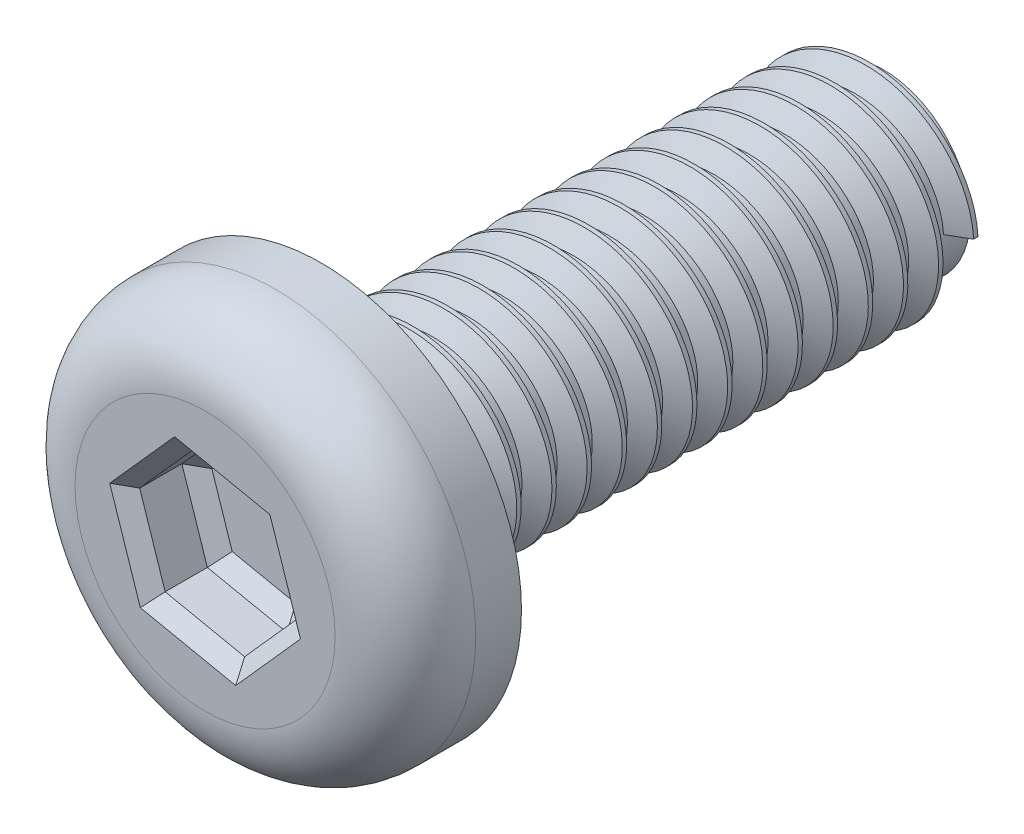
SolidWorks part; units mm, degrees
ref_plane "前视基准面" through (0, 0, 0) normal (0, 0, 1) x (1, 0, 0)
ref_plane "上视基准面" through (0, 0, 0) normal (0, 1, 0) x (1, 0, 0)
ref_plane "右视基准面" through (0, 0, 0) normal (1, 0, 0) x (0, 0, -1)
sketch "草图1" plane through (0, 0, 0) normal (0, 0, 1) x (1, 0, 0)
  circle A0 centre (0, 0) radius 2.85
  dimension "D1" = 5.7
extrude "凸台-拉伸1" add sketch "草图1" along normal blind 1.65
sketch "草图2" plane through (0, 0, 0) normal (0, 0, -1) x (-1, 0, 0)
  circle A0 centre (0, 0) radius 1.2295
  dimension "D1" = 2.459
extrude "凸台-拉伸2" add sketch "草图2" along normal blind 8
fillet "圆角1" radius 1 1 edges at (2.85, 0, 1.65)
sketch "草图3" plane through (0, 0, 1.65) normal (0, 0, 1) x (1, 0, 0)
  line L1 (0.3622, -1.0964) -> (1.1306, -0.2345)
  line L2 (1.1306, -0.2345) -> (0.7684, 0.8619)
  line L3 (0.7684, 0.8619) -> (-0.3622, 1.0964)
  line L4 (-0.3622, 1.0964) -> (-1.1306, 0.2345)
  line L5 (-1.1306, 0.2345) -> (-0.7684, -0.8619)
  line L6 (-0.7684, -0.8619) -> (0.3622, -1.0964)
  circle A0 centre (0, 0) radius 1 construction
  dimension "D1" = 2
extrude "切除-拉伸1" cut sketch "草图3" against normal blind 1
chamfer "倒角1" distance 0.2 angle 45 12 edges at (0.7464, -0.6655, 1.65) (0.9495, 0.3137, 1.65) (0.2031, 0.9792, 1.65) (-0.7464, 0.6655, 1.65) (-0.9495, -0.3137, 1.65) (-0.2031, -0.9792, 1.65) (-0.9495, -0.3137, 0.65) (-0.7464, 0.6655, 0.65) (0.2031, 0.9792, 0.65) (0.9495, 0.3137, 0.65) (0.7464, -0.6655, 0.65) (-0.2031, -0.9792, 0.65)
thread "螺纹线1" pitch 0.5 method extrude profile "螺纹线轮廓2" start angle 0, offset 0, length 0, pitch 0.5, diameter 2.459
ref_plane "基准面2" through (1.2295, 0, -8) normal (0, -1, 0) x (1, 0, 0)
sketch "螺纹线轮廓2" plane through (1.2295, 0, -8) normal (0, -1, 0) x (1, 0, 0)
  line L0 (0, 0) -> (0, 0.5) construction
  line L1 (0, 0) -> (0.2706, 0.1562)
  line L2 (0.2706, 0.1562) -> (0.2706, 0.2187)
  line L3 (0.2706, 0.2187) -> (0, 0.375)
  line L4 (0.2706, 0.1875) -> (0, 0.1875) construction
  line L11 (0, 0) -> (0, 0.375)
  point P2 (0, 0)
  dimension "Pitch" = 0.5
  dimension "Profile_Angle" = 60
  dimension "Profile_Land" = 0.0625
  dimension "Profile_Height" = 0.2706
